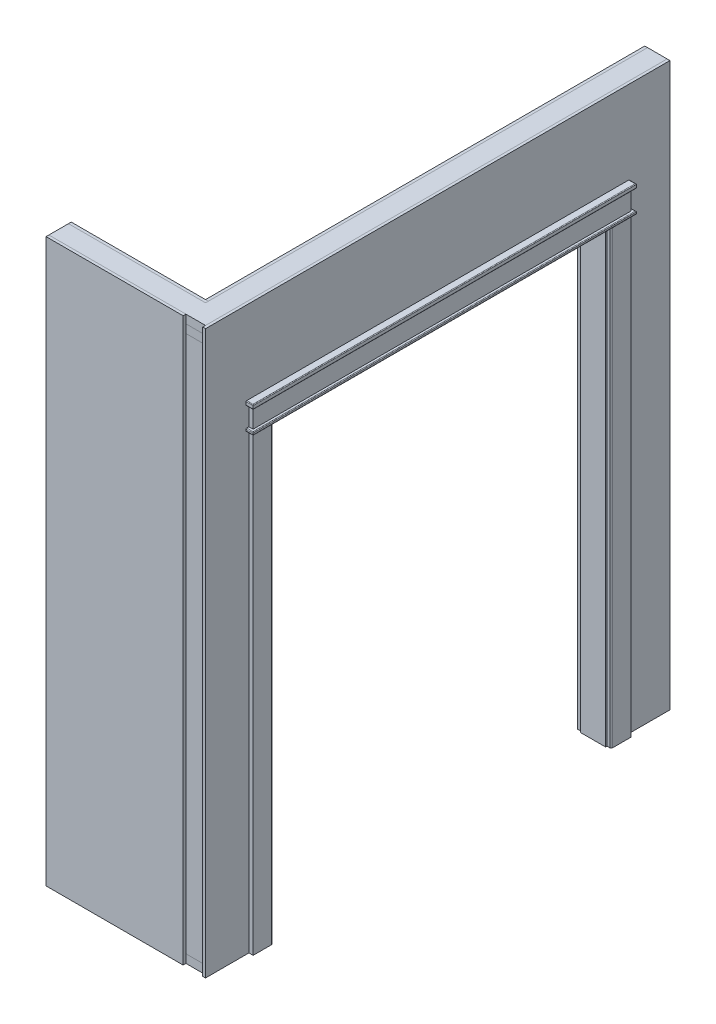
SolidWorks part; units mm, degrees
ref_plane "Front Plane" through (0, 0, 0) normal (0, 0, 1) x (1, 0, 0)
ref_plane "Top Plane" through (0, 0, 0) normal (0, 1, 0) x (1, 0, 0)
ref_plane "Right Plane" through (0, 0, 0) normal (1, 0, 0) x (0, 0, -1)
sketch "Sketch1" plane through (0, 0, 0) normal (0, 1, 0) x (1, 0, 0)
  line L1 (0, 0) -> (3581.4, 0)
  line L2 (0, 0) -> (0, 3479.8)
  line L3 (0, 3479.8) -> (3581.4, 3479.8)
  line L4 (3581.4, 0) -> (3581.4, 3479.8)
  line L9 (0, 76.2) -> (774.7, 76.2)
  line L10 (0, 1230.0171) -> (46.8505, 1230.0171)
  line L11 (0, 1230.0171) -> (0, 1143)
  line L12 (0, 1143) -> (46.8505, 1143)
  line L13 (46.8505, 1230.0171) -> (46.8505, 1143)
  line L14 (0, 76.2) -> (12.7, 76.2)
  line L15 (0, 977.9) -> (12.7, 977.9)
  line L16 (0, 977.9) -> (0, 850.9)
  line L17 (0, 850.9) -> (12.7, 850.9)
  line L18 (12.7, 977.9) -> (12.7, 850.9)
  line L19 (0, 76.2) -> (0, 0)
  line L20 (0, 0) -> (12.7, 0)
  line L21 (12.7, 76.2) -> (12.7, 0)
  arc A0 (0, 848.6682) -> (774.7, 76.2) centre (1.1159, 75.0841) cw
  dimension "D1" = 3581.4
  dimension "D2" = 3479.8
  dimension "D8" = 774.7
  dimension "D9" = 12.7
  dimension "D10" = 76.2
  dimension "D11" = 0
  dimension "D12" = 2249.7829
sketch "Sketch2" plane through (0, 0, 0) normal (0, 1, 0) x (1, 0, 0)
  line L0 (0, 0) -> (0, 3479.8) construction
  line L1 (0, 1473.2) -> (622.3, 1473.2)
  line L2 (0, 1473.2) -> (0, 1384.3)
  line L3 (0, 1384.3) -> (622.3, 1384.3)
  line L4 (622.3, 1473.2) -> (622.3, 1384.3)
  line L5 (0, 3479.8) -> (3581.4, 3479.8) construction
  dimension "D1" = 622.3
  dimension "D2" = 88.9
  dimension "D3" = 2006.6
extrude "Sole Plate 1" add sketch "Sketch2" along normal blind 38.1
sketch "Sketch3" plane through (0, 0, 0) normal (0, 1, 0) x (1, 0, 0)
  line L0 (711.2, 330.372) -> (711.2, 50330.372) construction
  line L1 (711.2, 1384.3) -> (622.3, 1384.3)
  line L2 (711.2, 1384.3) -> (711.2, 1644.65)
  line L3 (711.2, 1644.65) -> (622.3, 1644.65)
  line L4 (622.3, 1384.3) -> (622.3, 1644.65)
  line L5 (-1000, 3479.8) -> (49000, 3479.8) construction
  line L6 (0, 0) -> (0, 3479.8) construction
  line L7 (711.2, 3479.8) -> (622.3, 3479.8)
  line L8 (711.2, 3479.8) -> (711.2, 3206.75)
  line L9 (711.2, 3206.75) -> (622.3, 3206.75)
  line L10 (622.3, 3479.8) -> (622.3, 3206.75)
  line L12 (622.3, 1473.2) -> (0, 1473.2) construction
  dimension "D1" = 88.9
  dimension "D2" = 260.35
  dimension "D3" = 273.05
  dimension "D4" = 0
  dimension "D5" = 88.9
  dimension "D6" = 711.2
  dimension "D7" = 1562.1
  dimension "D8" = 2006.6
extrude "Sole Plate 2" add sketch "Sketch3" along normal blind 38.1 separate body
sketch "Sketch5" plane through (0, 38.1, 0) normal (0, 1, 0) x (1, 0, 0)
  line L1 (711.2, 1384.3) -> (622.3, 1384.3)
  line L2 (711.2, 1384.3) -> (711.2, 1422.4)
  line L3 (711.2, 1422.4) -> (622.3, 1422.4)
  line L4 (622.3, 1384.3) -> (622.3, 1422.4)
  line L5 (622.3, 1460.5) -> (711.2, 1460.5)
  line L6 (622.3, 1460.5) -> (622.3, 1498.6)
  line L7 (622.3, 1498.6) -> (711.2, 1498.6)
  line L8 (711.2, 1460.5) -> (711.2, 1498.6)
  line L9 (711.2, 1644.65) -> (622.3, 1644.65) construction
  line L10 (711.2, 1384.3) -> (711.2, 1644.65) construction
  line L14 (0, 1384.3) -> (622.3, 1384.3) construction
  line L15 (622.3, 1473.2) -> (0, 1473.2) construction
  line L16 (0, 1473.2) -> (38.1, 1473.2)
  line L17 (0, 1473.2) -> (0, 1384.3)
  line L18 (0, 1384.3) -> (38.1, 1384.3)
  line L19 (38.1, 1473.2) -> (38.1, 1384.3)
  line L20 (406.4, 1473.2) -> (444.5, 1473.2)
  line L21 (406.4, 1473.2) -> (406.4, 1384.3)
  line L22 (406.4, 1384.3) -> (444.5, 1384.3)
  line L23 (444.5, 1473.2) -> (444.5, 1384.3)
  line L24 (622.3, 1644.65) -> (622.3, 1384.3) construction
  line L25 (711.2, 3206.75) -> (711.2, 3479.8) construction
  line L26 (622.3, 3479.8) -> (711.2, 3479.8)
  line L27 (622.3, 3479.8) -> (622.3, 3441.7)
  line L28 (622.3, 3441.7) -> (711.2, 3441.7)
  line L29 (711.2, 3479.8) -> (711.2, 3441.7)
  line L30 (711.2, 1606.55) -> (622.3, 1606.55)
  line L31 (711.2, 1606.55) -> (711.2, 1568.45)
  line L32 (711.2, 1568.45) -> (622.3, 1568.45)
  line L33 (622.3, 1606.55) -> (622.3, 1568.45)
  line L34 (622.3, 3479.8) -> (622.3, 3206.75) construction
  line L35 (622.3, 3282.95) -> (711.2, 3282.95)
  line L36 (622.3, 3282.95) -> (622.3, 3244.85)
  line L37 (622.3, 3244.85) -> (711.2, 3244.85)
  line L38 (711.2, 3282.95) -> (711.2, 3244.85)
  line L39 (622.3, 3206.75) -> (711.2, 3206.75) construction
  dimension "D1" = 88.9
  dimension "D2" = 38.1
  dimension "D3" = 88.9
  dimension "D4" = 38.1
  dimension "D5" = 38.1
  dimension "D6" = 38.1
  dimension "D7" = 38.1
  dimension "D8" = 406.4
  dimension "D9" = 38.1
  dimension "D10" = 38.1
  dimension "D11" = 38.1
  dimension "D12" = 38.1
  dimension "D13" = 76.2
extrude "Framing Studs" add sketch "Sketch5" along normal blind 2438.4 separate body
sketch "Sketch6" plane through (0, 38.1, 0) normal (0, 1, 0) x (1, 0, 0)
  line L1 (622.3, 3244.85) -> (711.2, 3244.85)
  line L2 (622.3, 3244.85) -> (622.3, 3206.75)
  line L3 (622.3, 3206.75) -> (711.2, 3206.75)
  line L4 (711.2, 3244.85) -> (711.2, 3206.75)
  line L5 (622.3, 1644.65) -> (711.2, 1644.65)
  line L6 (622.3, 1644.65) -> (622.3, 1606.55)
  line L7 (622.3, 1606.55) -> (711.2, 1606.55)
  line L8 (711.2, 1644.65) -> (711.2, 1606.55)
extrude "Jack Studs" add sketch "Sketch6" along normal blind 2030.4125 separate body
sketch "Sketch7" plane through (0, 2068.5125, 0) normal (0, 1, 0) x (1, 0, 0)
  line L0 (622.3, 1606.55) -> (711.2, 1606.55) construction
  line L1 (622.3, 1606.55) -> (711.2, 1606.55)
  line L2 (622.3, 1606.55) -> (622.3, 3244.85)
  line L3 (622.3, 3244.85) -> (711.2, 3244.85)
  line L4 (711.2, 1606.55) -> (711.2, 3244.85)
  dimension "D1" = 0
extrude "Header" add sketch "Sketch7" along normal blind 38.1 separate body
sketch "Sketch8" plane through (0, 2106.6125, 0) normal (0, 1, 0) x (1, 0, 0)
  line L1 (622.3, 1606.55) -> (711.2, 1606.55)
  line L2 (622.3, 1606.55) -> (622.3, 1644.65)
  line L3 (622.3, 1644.65) -> (711.2, 1644.65)
  line L4 (711.2, 1606.55) -> (711.2, 1644.65)
  line L5 (622.3, 2012.95) -> (711.2, 2012.95)
  line L6 (622.3, 3244.85) -> (711.2, 3244.85)
  line L7 (622.3, 3244.85) -> (622.3, 3206.75)
  line L8 (622.3, 3206.75) -> (711.2, 3206.75)
  line L9 (711.2, 3244.85) -> (711.2, 3206.75)
  line L10 (622.3, 2012.95) -> (622.3, 2051.05)
  line L11 (622.3, 2051.05) -> (711.2, 2051.05)
  line L12 (711.2, 2012.95) -> (711.2, 2051.05)
  line L13 (622.3, 2419.35) -> (711.2, 2419.35)
  line L14 (622.3, 2419.35) -> (622.3, 2457.45)
  line L15 (622.3, 2457.45) -> (711.2, 2457.45)
  line L16 (711.2, 2419.35) -> (711.2, 2457.45)
  line L17 (622.3, 2825.75) -> (711.2, 2825.75)
  line L18 (622.3, 2825.75) -> (622.3, 2863.85)
  line L19 (622.3, 2863.85) -> (711.2, 2863.85)
  line L20 (711.2, 2825.75) -> (711.2, 2863.85)
  dimension "D1" = 38.1
  dimension "D2" = 38.1
  dimension "D3" = 4
extrude "Cripple Studs" add sketch "Sketch8" along normal up to surface (369.8875 mm away) separate body up to face at (666.75, 2476.5, -3263.9)
sketch "Sketch9" plane through (0, 2476.5, 0) normal (0, 1, 0) x (1, 0, 0)
  line L1 (622.3, 1473.2) -> (0, 1473.2)
  line L2 (622.3, 1473.2) -> (622.3, 1384.3)
  line L3 (622.3, 1384.3) -> (0, 1384.3)
  line L4 (0, 1473.2) -> (0, 1384.3)
  line L5 (711.2, 1384.3) -> (622.3, 1384.3)
  line L6 (711.2, 1384.3) -> (711.2, 3479.8)
  line L7 (711.2, 3479.8) -> (622.3, 3479.8)
  line L8 (622.3, 1384.3) -> (622.3, 3479.8)
  line M14 (711.2, 1384.3) -> (711.2, 1422.4)
  line M15 (711.2, 1422.4) -> (622.3, 1422.4)
  line M16 (622.3, 1422.4) -> (622.3, 1384.3)
  line M17 (622.3, 1384.3) -> (711.2, 1384.3)
extrude "Top Plate 1" add sketch "Sketch9" along normal blind 38.1 separate body contours L3 L2 L1 | L8 L2 L5 L6 L7 | M17 M14 M15 M16 region at (311.15, 2476.5, -1428.75) region at (666.75, 2476.5, -2451.1) region at (666.75, 2476.5, -1403.35)
sketch "Sketch10" plane through (0, 0, -1473.2) normal (0, 0, -1) x (-1, 0, 0)
  line L1 (0, 2552.7) -> (-622.3, 2552.7)
  line L2 (0, 2552.7) -> (0, 0)
  line L3 (0, 0) -> (-622.3, 0)
  line L4 (-622.3, 2552.7) -> (-622.3, 0)
extrude "Inside Side Wall Dry Wall" add sketch "Sketch10" along normal blind 12.7 separate body
sketch "Sketch11" plane through (622.3, 0, 0) normal (-1, 0, 0) x (0, 0, 1)
  line L0 (-1485.9, 0) -> (-1485.9, 2552.7)
  line L1 (-1485.9, 2552.7) -> (-3479.8, 2552.7)
  line L2 (-3479.8, 2552.7) -> (-3479.8, 0)
  line L3 (-3479.8, 0) -> (-3206.75, 0)
  line L4 (-3206.75, 0) -> (-3206.75, 2068.5125)
  line L5 (-3206.75, 2068.5125) -> (-1644.65, 2068.5125)
  line L6 (-1644.65, 2068.5125) -> (-1644.65, 0)
  line L7 (-1644.65, 0) -> (-1485.9, 0)
  line L8 (-1473.2, 2514.6) -> (-3479.8, 2514.6) construction
  dimension "D1" = 38.1
extrude "Inside Main Wall Dry Wall" add sketch "Sketch11" along normal blind 12.7 separate body
sketch "Sketch12" plane through (0, 0, -1384.3) normal (0, 0, 1) x (1, 0, 0)
  line L1 (0, 2552.7) -> (622.3, 2552.7)
  line L2 (0, 2552.7) -> (0, 0)
  line L3 (0, 0) -> (622.3, 0)
  line L4 (622.3, 2552.7) -> (622.3, 0)
extrude "Outside Side Wall Dry Wall" add sketch "Sketch12" along normal blind 12.7 separate body
sketch "Sketch13" plane through (711.2, 0, 0) normal (1, 0, 0) x (0, 0, -1)
  line L0 (3479.8, 0) -> (3206.75, 0)
  line L1 (3206.75, 0) -> (3206.75, 2068.5125)
  line L2 (3206.75, 2068.5125) -> (1644.65, 2068.5125)
  line L3 (1644.65, 2068.5125) -> (1644.65, 0)
  line L4 (1644.65, 0) -> (1371.6, 0)
  line L5 (1371.6, 0) -> (1371.6, 2552.7)
  line L6 (1371.6, 2552.7) -> (3479.8, 2552.7)
  line L7 (3479.8, 2552.7) -> (3479.8, 0)
  line L9 (1384.3, 2476.5) -> (3479.8, 2476.5) construction
  dimension "D1" = 76.2
extrude "Outside Main Wall Dry Wall" add sketch "Sketch13" along normal blind 12.7 separate body
sketch "Sketch21" plane through (0, 2514.6, 0) normal (0, 1, 0) x (1, 0, 0)
  line L0 (622.3, 3479.8) -> (622.3, 1473.2)
  line L1 (622.3, 1473.2) -> (0, 1473.2)
  line L2 (0, 1473.2) -> (0, 1384.3)
  line L3 (0, 1384.3) -> (711.2, 1384.3)
  line L4 (711.2, 1384.3) -> (711.2, 3479.8)
  line L5 (711.2, 3479.8) -> (622.3, 3479.8)
extrude "Top Plate 2" add sketch "Sketch21" along normal blind 38.1 separate body
sketch "Sketch14" plane through (723.9, 0, 0) normal (1, 0, 0) x (0, 0, -1)
  line L0 (1644.65, 2068.5125) -> (3206.75, 2068.5125) construction
  line L1 (1657.35, 0) -> (1568.45, 0)
  line L2 (1657.35, 0) -> (1657.35, 2055.8125)
  line L3 (1657.35, 2055.8125) -> (1568.45, 2055.8125)
  line L4 (1568.45, 0) -> (1568.45, 2055.8125)
  line L5 (1555.75, 2068.5125) -> (3295.65, 2068.5125)
  line L6 (3194.05, 0) -> (3282.95, 0)
  line L7 (3194.05, 0) -> (3194.05, 2055.8125)
  line L8 (3194.05, 2055.8125) -> (3282.95, 2055.8125)
  line L9 (3282.95, 0) -> (3282.95, 2055.8125)
  line L10 (1568.45, 2055.8125) -> (3295.65, 2055.8125)
  line L11 (1555.75, 2068.5125) -> (1555.75, 2055.8125)
  line L12 (3295.65, 2055.8125) -> (1555.75, 2055.8125)
  line L13 (3295.65, 2055.8125) -> (3295.65, 2068.5125)
  line L14 (1568.45, 2068.5125) -> (3282.95, 2068.5125)
  line L15 (1568.45, 2068.5125) -> (1568.45, 2157.4125)
  line L16 (1568.45, 2157.4125) -> (3282.95, 2157.4125)
  line L17 (3282.95, 2068.5125) -> (3282.95, 2157.4125)
  line L18 (1555.75, 2176.4625) -> (3295.65, 2176.4625)
  line L19 (1555.75, 2176.4625) -> (1555.75, 2157.4125)
  line L20 (1568.45, 2157.4125) -> (3295.65, 2157.4125)
  line L21 (3295.65, 2176.4625) -> (3295.65, 2157.4125)
  line L22 (1555.75, 2055.8125) -> (1568.45, 2055.8125)
  line L23 (1644.65, 0) -> (1644.65, 2068.5125) construction
  line L24 (3206.75, 2068.5125) -> (3206.75, 0) construction
  line L25 (1555.75, 2157.4125) -> (1568.45, 2157.4125)
  line M4 (1371.6, 0) -> (1644.65, 0)
  line M5 (1644.65, 0) -> (1644.65, 2068.5125)
  line M7 (3206.75, 2068.5125) -> (3206.75, 0)
  line M8 (3206.75, 0) -> (3479.8, 0)
  dimension "D2" = 88.9
  dimension "D3" = 88.9
  dimension "D4" = 0
  dimension "D5" = 12.7
  dimension "D6" = 12.7
  dimension "D7" = 12.7
  dimension "D8" = 88.9
  dimension "D9" = 19.05
  dimension "D10" = 12.7
  dimension "D11" = 0
  dimension "D12" = 0
  dimension "D13" = 12.7
  dimension "D14" = 12.7
  dimension "D15" = 12.7
  dimension "D16" = 0
  dimension "D17" = 0
  dimension "D18" = 12.7
  dimension "D19" = 0
extrude "Casing Flat" add sketch "Sketch14" along normal blind 19.05 separate body contours L4 L3 M4 M5 | L17 L16 L15 | L9 L8 M8 M7 | L2 L3 L1 M5 | L8 L7 L6 M7 region at (723.9, 1027.9062, -1651) region at (723.9, 1027.9062, -1606.55) region at (723.9, 1027.9062, -3200.4) region at (723.9, 2112.9625, -2425.7) region at (723.9, 1027.9062, -3244.85)
extrude "Casing Fillet" add sketch "Sketch14<3>" along normal blind 31.75 contours L21 L18 L19 L20 L16 | L3 L10 L8 L5 M7 M5 | L12 L3 L5 L11 M5 | L10 L13 L5 L8 M7 region at (723.9, 2062.1625, -2425.7) region at (723.9, 2062.1625, -1600.2) region at (723.9, 2062.1625, -3251.2) region at (723.9, 2166.9375, -2425.7)
sketch "Sketch14<3>" plane through (723.9, 0, 0) normal (1, 0, 0) x (0, 0, -1) same geometry as "Sketch14"
fillet "Fillet1" radius 3.175 12 edges at (739.775, 2176.4625, -1555.75) (739.775, 2157.4125, -1555.75) (755.65, 2176.4625, -2425.7) (755.65, 2157.4125, -2425.7) (739.775, 2176.4625, -3295.65) (739.775, 2157.4125, -3295.65) (739.775, 2055.8125, -3295.65) (739.775, 2055.8125, -1555.75) (755.65, 2055.8125, -2425.7) (739.775, 2068.5125, -3295.65) (755.65, 2068.5125, -2425.7) (739.775, 2068.5125, -1555.75)
fillet "Fillet2" radius 6.35 2 edges at (742.95, 1027.9062, -1657.35) (742.95, 1027.9062, -3194.05)
sketch "Sketch17" plane through (0, 2068.5125, 0) normal (0, -1, 0) x (-1, 0, 0)
  line L1 (-609.6, 1644.65) -> (-723.9, 1644.65)
  line L2 (-609.6, 1644.65) -> (-609.6, 3206.75)
  line L3 (-609.6, 3206.75) -> (-723.9, 3206.75)
  line L4 (-723.9, 1644.65) -> (-723.9, 3206.75)
  dimension "D1" = 114.3
extrude "Trim Door Top" add sketch "Sketch17" along normal blind 19.05 separate body
sketch "Sketch18" plane through (0, 0, -3206.75) normal (0, 0, 1) x (1, 0, 0)
  line L1 (609.6, 2049.4625) -> (723.9, 2049.4625)
  line L2 (609.6, 2049.4625) -> (609.6, 0)
  line L3 (609.6, 0) -> (723.9, 0)
  line L4 (723.9, 2049.4625) -> (723.9, 0)
extrude "Trim Door Right" add sketch "Sketch18" along normal blind 19.05 separate body
sketch "Sketch19" plane through (0, 0, -1644.65) normal (0, 0, -1) x (-1, 0, 0)
  line L1 (-723.9, 2049.4625) -> (-609.6, 2049.4625)
  line L2 (-723.9, 2049.4625) -> (-723.9, 0)
  line L3 (-723.9, 0) -> (-609.6, 0)
  line L4 (-609.6, 2049.4625) -> (-609.6, 0)
extrude "Trim Door Left" add sketch "Sketch19" along normal blind 19.05 separate body
sketch "Sketch20" plane through (609.6, 0, 0) normal (-1, 0, 0) x (0, 0, 1)
  line L0 (-3187.7, 0) -> (-3206.75, 0) construction
  line L1 (-1657.35, 0) -> (-1619.25, 0)
  line L2 (-1657.35, 0) -> (-1657.35, 2055.8125)
  line L3 (-1657.35, 2055.8125) -> (-1619.25, 2055.8125)
  line L4 (-1619.25, 0) -> (-1619.25, 2055.8125)
  line L5 (-3194.05, 0) -> (-3232.15, 0)
  line L6 (-3194.05, 0) -> (-3194.05, 2055.8125)
  line L7 (-3194.05, 2055.8125) -> (-3232.15, 2055.8125)
  line L8 (-3232.15, 0) -> (-3232.15, 2055.8125)
  line L9 (-3232.15, 2055.8125) -> (-1619.25, 2055.8125)
  line L10 (-3232.15, 2055.8125) -> (-3232.15, 2093.9125)
  line L11 (-3232.15, 2093.9125) -> (-1619.25, 2093.9125)
  line L12 (-1619.25, 2055.8125) -> (-1619.25, 2093.9125)
  line L14 (-1663.7, 0) -> (-1663.7, 2049.4625) construction
  line L15 (-3187.7, 2049.4625) -> (-3187.7, 0) construction
  line L16 (-1644.65, 2049.4625) -> (-3206.75, 2049.4625) construction
  line M6 (-3206.75, 0) -> (-3206.75, 2068.5125)
  line M7 (-3206.75, 2068.5125) -> (-1644.65, 2068.5125)
  line M8 (-1644.65, 2068.5125) -> (-1644.65, 0)
  dimension "D1" = 38.1
  dimension "D2" = 38.1
  dimension "D3" = 38.1
  dimension "D4" = 6.35
  dimension "D5" = 6.35
  dimension "D6" = 6.35
extrude "Casing Door interior Sides" add sketch "Sketch20" along normal blind 19.05 separate body contours L3 L2 L1 L4 | L7 L6 L5 L8
extrude "Casing Door Interior Top" add sketch "Sketch20<4>" along normal blind 19.05 separate body contours L3 L12 L11 L10 L7 M6 M7 M8 | L7 L9 L3 M8 M7 M6 region at (609.6, 2062.1625, -2425.7) region at (609.6, 2080.9172, -2425.7)
sketch "Sketch20<4>" plane through (609.6, 0, 0) normal (-1, 0, 0) x (0, 0, 1) same geometry as "Sketch20"
sketch "Sketch23" plane through (0, 38.1, 0) normal (0, 1, 0) x (1, 0, 0)
  line L0 (622.3, 1473.2) -> (0, 1473.2) construction
  line L1 (622.3, 1384.3) -> (584.2, 1384.3)
  line L2 (622.3, 1384.3) -> (622.3, 1473.2)
  line L3 (622.3, 1473.2) -> (584.2, 1473.2)
  line L4 (584.2, 1384.3) -> (584.2, 1473.2)
  dimension "D1" = 38.1
extrude "Boss-Extrude1" add sketch "Sketch23" along normal blind 2438.4 separate body
